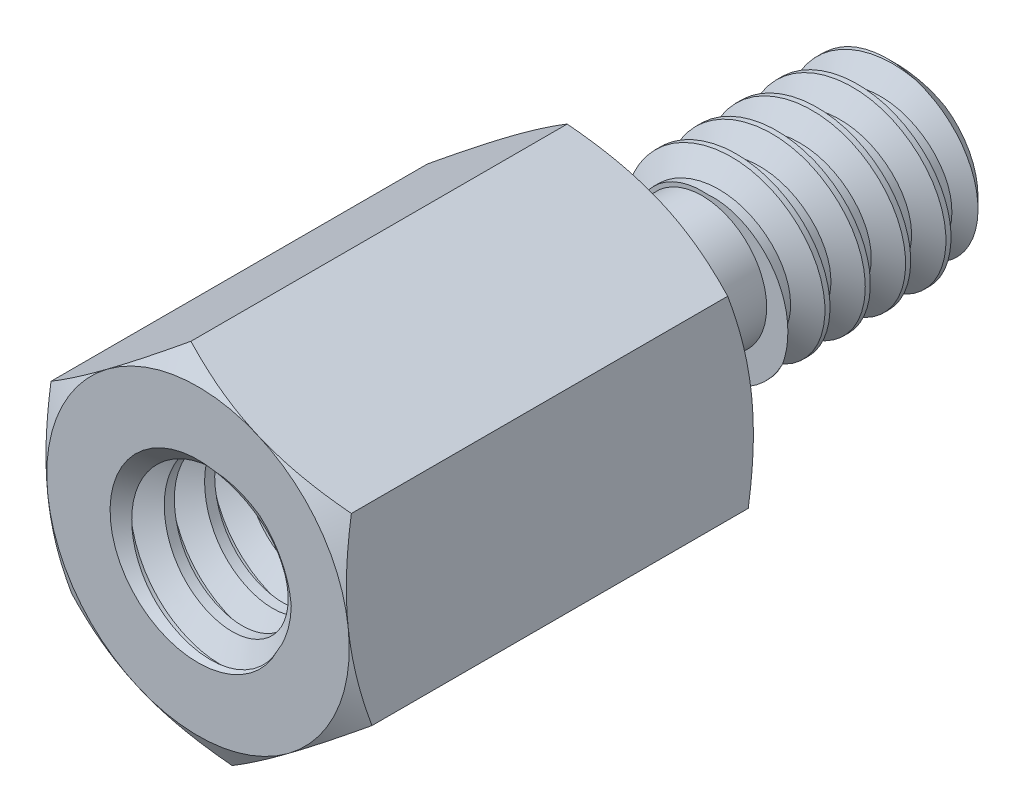
SolidWorks part; units mm, degrees
ref_plane "Front Plane" through (0, 0, 0) normal (0, 0, 1) x (1, 0, 0)
ref_plane "Top Plane" through (0, 0, 0) normal (0, 1, 0) x (1, 0, 0)
ref_plane "Right Plane" through (0, 0, 0) normal (1, 0, 0) x (0, 0, -1)
sketch "Sketch1" plane through (0, 0, 0) normal (0, 0, 1) x (1, 0, 0)
  line L1 (2.2024, 1.6461) -> (-0.3244, 2.7304)
  line L2 (-0.3244, 2.7304) -> (-2.5268, 1.0843)
  line L3 (-2.5268, 1.0843) -> (-2.2024, -1.6461)
  line L4 (-2.2024, -1.6461) -> (0.3244, -2.7304)
  line L5 (0.3244, -2.7304) -> (2.5268, -1.0843)
  line L6 (2.5268, -1.0843) -> (2.2024, 1.6461)
  circle A0 centre (0, 0) radius 2.3813 construction
  dimension "D1" = 4.7625
  dimension "D2" = 0.3244
extrude "Boss-Extrude1" add sketch "Sketch1" along normal blind 6.35
sketch "Sketch2" plane through (0, 0, 6.35) normal (0, 0, 1) x (1, 0, 0)
  circle A0 centre (0, 0) radius 2.3813
  dimension "D1" = 4.7625
extrude "Cut-Extrude1" cut sketch "Sketch2" against normal blind 2.286 draft 60 flip side to cut
sketch "Sketch3" plane through (0, 0, 0) normal (0, 0, -1) x (-1, 0, 0)
  circle A0 centre (0, 0) radius 2.3813
extrude "Cut-Extrude2" cut sketch "Sketch3" against normal blind 2.286 draft 60 flip side to cut
hole_wizard "Tap Drill for #4-40 Tap1" positions "Sketch4" profile "Sketch6" hole size "#4-40" standard "ANSI Inch"
sketch "Sketch4" plane through (0, 0, 6.35) normal (0, 0, 1) x (1, 0, 0)
  point P0 (0, 0)
sketch "Sketch6" plane through (0, 0, 6.35) normal (1, 0, 0) x (0, -1, 0)
  line L0 (0, 0) -> (0, 5.7592)
  line L1 (0, 5.7592) -> (1.1303, 5.08)
  line L2 (1.1303, 5.08) -> (1.1303, 0)
  line L5 (1.1303, 0) -> (0, 0)
  line L10 (0, 5.7592) -> (-1.1303, 5.08) construction
  line L11 (0, -6.35) -> (0, 107.95) construction
  dimension "Hole Dia." = 2.2606
  dimension "Hole Depth" = 5.08
  dimension "Drill Angle" = 118
chamfer "Chamfer2" distance 0.254 angle 45 1 edges at (1.1303, 0, 6.35)
thread "Thread1" pitch 0.635 start angle 0, offset 0.762, length 0, pitch 0.635, diameter 2.2606
ref_plane "Plane1" through (-1.1303, 0, 6.858) normal (0, -1, 0) x (-1, 0, 0)
sketch "Thread Profile1" plane through (-1.1303, 0, 6.858) normal (0, -1, 0) x (-1, 0, 0)
  line L0 (0, 0) -> (0, 0.635) construction
  line L1 (0, 0) -> (0.3437, 0.1984)
  line L2 (0.3437, 0.1984) -> (0.3437, 0.2778)
  line L3 (0.3437, 0.2778) -> (0, 0.4762)
  line L4 (0.3437, 0.2381) -> (0, 0.2381) construction
  line L11 (0, 0) -> (0, 0.4762)
  point P2 (0, 0)
  dimension "Pitch" = 0.635
  dimension "Profile_Angle" = 60
  dimension "Profile_Land" = 0.0794
  dimension "Profile_Height" = 0.3437
sketch "Sketch11" plane through (0, 0, 0) normal (0, 0, -1) x (-1, 0, 0)
  circle A0 centre (0, 0) radius 1.016
  dimension "D1" = 2.032
extrude "Boss-Extrude2" add sketch "Sketch11" along normal blind 1.5875
sketch "Sketch12" plane through (0, 0, -1.5875) normal (0, 0, -1) x (-1, 0, 0)
  circle A0 centre (0, 0) radius 1.4224
  dimension "D1" = 2.8448
extrude "Boss-Extrude3" add sketch "Sketch12" along normal blind 3.175
chamfer "Chamfer1" distance 0.254 angle 45 1 edges at (-1.4224, 0, -4.7625)
thread "Thread2" pitch 0.635 profile "Thread Profile2" start angle 0, offset 0.762, length 0, pitch 0.635, diameter 2.8448
ref_plane "Plane2" through (1.4224, 0, -5.2705) normal (0, -1, 0) x (1, 0, 0)
sketch "Thread Profile2" plane through (1.4224, 0, -5.2705) normal (0, -1, 0) x (1, 0, 0)
  line L0 (0, 0) -> (0, 0.635) construction
  line L11 (0, 0) -> (0, 0.5556)
  line L12 (0, 0.5556) -> (-0.3437, 0.3572)
  line L13 (-0.3437, 0.3572) -> (-0.3437, 0.1984)
  line L15 (-0.3437, 0.1984) -> (0, 0)
  line L17 (-0.3437, 0.2778) -> (0, 0.2778) construction
  point P2 (0, 0)
  dimension "Pitch" = 0.635
  dimension "Profile_Angle" = 60
  dimension "Profile_Land" = 0.1588
  dimension "Profile_Height" = 0.3437
